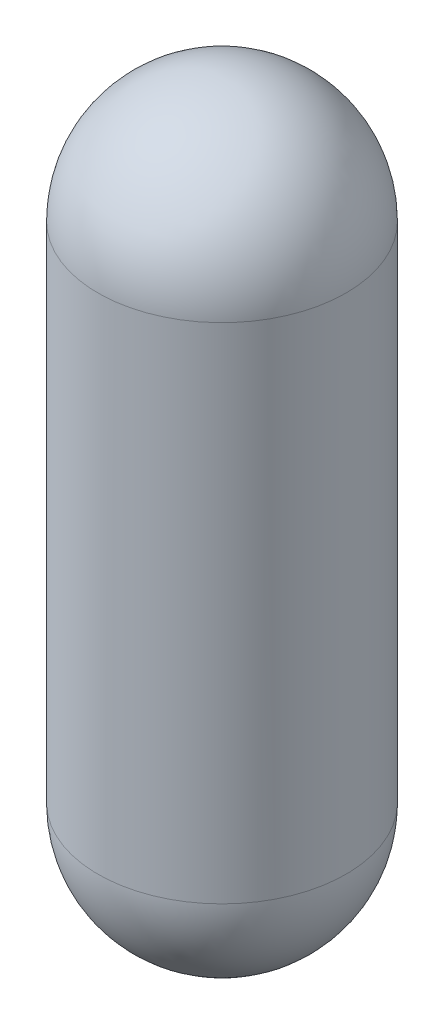
SolidWorks part; units mm, degrees
ref_plane "Front Plane" through (0, 0, 0) normal (0, 0, 1) x (1, 0, 0)
ref_plane "Top Plane" through (0, 0, 0) normal (0, 1, 0) x (1, 0, 0)
ref_plane "Right Plane" through (0, 0, 0) normal (1, 0, 0) x (0, 0, -1)
sketch "Sketch1" plane through (0, 0, 0) normal (0, 0, 1) x (1, 0, 0)
  line L0 (0, 1339.6) -> (0, 1669.8)
  line L2 (0, 0) -> (0, 1339.6)
  line L4 (330.2, 0) -> (330.2, 1339.6)
  line L5 (0, -330.2) -> (0, 0)
  line L6 (0, 976.2421) -> (330.2, 976.2421) construction
  arc A2 (330.2, 1339.6) -> (0, 1669.8) centre (0, 1339.6) ccw
  arc A3 (0, -330.2) -> (330.2, 0) centre (0, 0) ccw
  dimension "D1" = 2000
  dimension "D2" = 330.2
revolve "Revolve1" add sketch "Sketch1" angle 360 about L2
